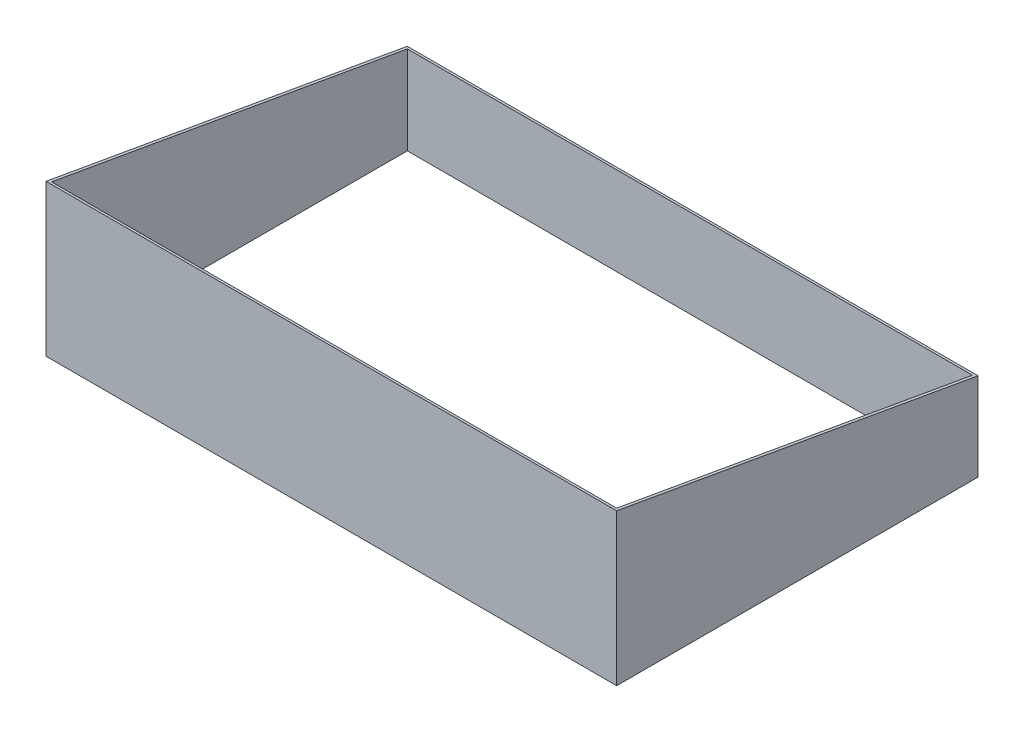
SolidWorks part; units mm, degrees
ref_plane "Front Plane" through (0, 0, 0) normal (0, 0, 1) x (1, 0, 0)
ref_plane "Top Plane" through (0, 0, 0) normal (0, 1, 0) x (1, 0, 0)
ref_plane "Right Plane" through (0, 0, 0) normal (1, 0, 0) x (0, 0, -1)
sketch "Sketch1" plane through (0, 0, 0) normal (1, 0, 0) x (0, 0, -1)
  line L0 (0, 345.1265) -> (0, 0)
  line L1 (0, 0) -> (823.0531, 0)
  line L4 (823.0531, 0) -> (823.0531, 200)
  line L5 (0, 345.1265) -> (823.0531, 200)
  dimension "D1" = 10
  dimension "D2" = 835.75
  dimension "D3" = 200
extrude "Boss-Extrude1" add sketch "Sketch1" along normal blind 1300
shell "Shell1" thickness 6.35 removed face at (650, 0, -411.5265) removed face at (650, 272.5632, -411.5265)
